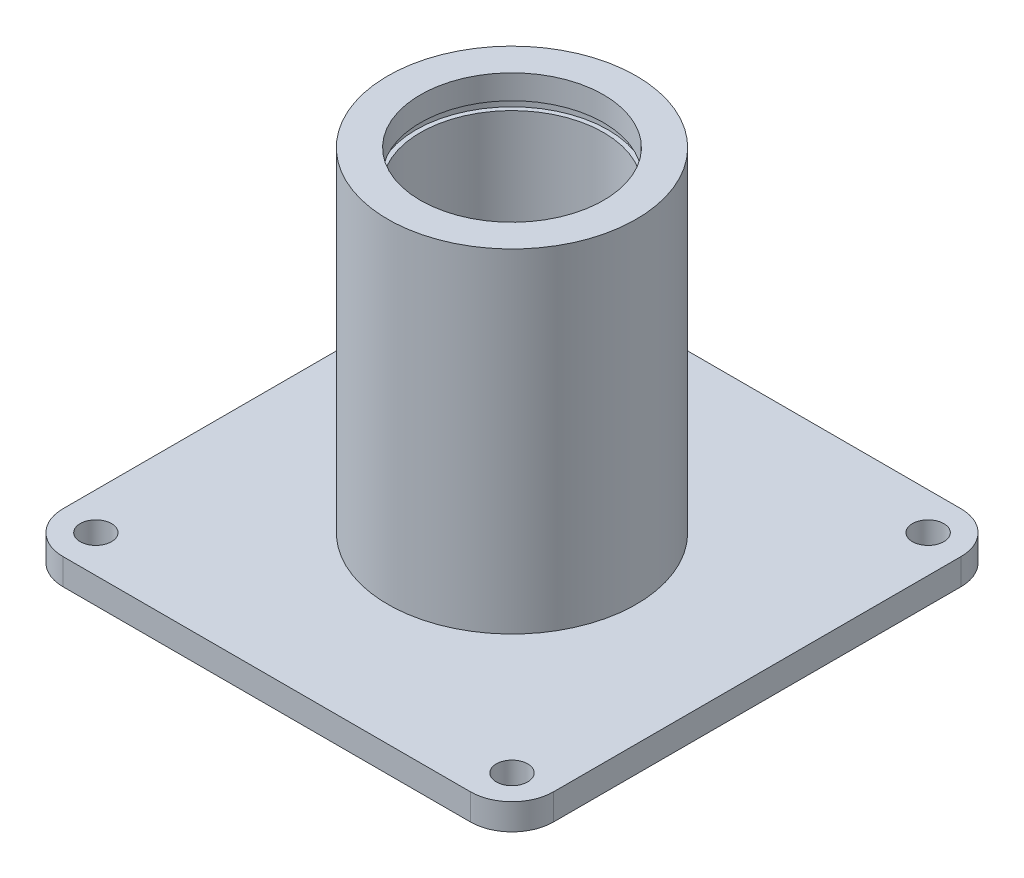
SolidWorks part; units mm, degrees
ref_plane "Front Plane" through (0, 0, 0) normal (0, 0, 1) x (1, 0, 0)
ref_plane "Top Plane" through (0, 0, 0) normal (0, 1, 0) x (1, 0, 0)
ref_plane "Right Plane" through (0, 0, 0) normal (1, 0, 0) x (0, 0, -1)
ref_axis "X" through (88.99, 0, 0) along (-1, 0, 0)
ref_axis "Y" through (0, 55, 0) along (0, -1, 0)
ref_axis "Z" through (0, 0, -88.99) along (0, 0, 1)
sketch "Sketch1" plane through (0, 0, 0) normal (0, 0, 1) x (1, 0, 0)
  line L0 (0, 0) -> (0, 52.8087) construction
  line L1 (-12, 0) -> (-29, 0)
  line L2 (-29, 0) -> (-29, 4)
  line L3 (-29, 4) -> (-19, 4)
  line L4 (-19, 4) -> (-19, 55)
  line L5 (-19, 55) -> (-14, 55)
  line L6 (-14, 55) -> (-14, 51.3)
  line L7 (-14, 30) -> (-12, 30)
  line L8 (-12, 30) -> (-12, 0)
  line L10 (-14, 51.3) -> (-14.7, 51.3)
  line L12 (-14, 50) -> (-14.7, 50)
  line L13 (-14.7, 51.3) -> (-14.7, 50)
  line L14 (-14, 50) -> (-14, 30)
  dimension "D1" = 28
  dimension "D2" = 30
  dimension "D3" = 24
  dimension "D4" = 38
  dimension "D5" = 10
  dimension "D6" = 4
  dimension "D7" = 1.3
  dimension "D8" = 29.4
  dimension "D9" = 55
  dimension "D10" = 20
revolve "Revolve1" add sketch "Sketch1" angle 360 about L0
sketch "Sketch2" plane through (0, 4, 0) normal (0, 1, 0) x (1, 0, 0)
  line L1 (37.5, -37.5) -> (-37.5, -37.5)
  line L2 (37.5, -37.5) -> (37.5, 37.5)
  line L3 (37.5, 37.5) -> (-37.5, 37.5)
  line L4 (-37.5, -37.5) -> (-37.5, 37.5)
  line L5 (37.5, -37.5) -> (-37.5, 37.5) construction
  line L6 (37.5, 37.5) -> (-37.5, -37.5) construction
  circle A0 centre (0, 0) radius 21
  point P0 (0, 0)
  dimension "D1" = 75
extrude "Boss-Extrude1" add sketch "Sketch2" against normal up to surface (4 mm away) up to face at (0, 0, -12)
hole_wizard "M4 Clearance Hole1" positions "Sketch3" profile "Sketch4" hole size "M4" standard "DIN" end condition up to next
sketch "Sketch3" plane through (0, 0, 0) normal (0, -1, 0) x (-1, 0, 0)
  line L2 (31.8198, -31.8198) -> (-31.8198, -31.8198)
  line L3 (31.8198, -31.8198) -> (31.8198, 31.8198)
  line L4 (31.8198, 31.8198) -> (-31.8198, 31.8198)
  line L5 (-31.8198, -31.8198) -> (-31.8198, 31.8198)
  line L6 (31.8198, -31.8198) -> (-31.8198, 31.8198) construction
  line L7 (31.8198, 31.8198) -> (-31.8198, -31.8198) construction
  point P16 (0, 0)
  point P61 (-31.8198, 31.8198)
  point P64 (31.8198, 31.8198)
  point P67 (31.8198, -31.8198)
  point P70 (-31.8198, -31.8198)
  dimension "D1" = 90
sketch "Sketch4" plane through (0, 0, 0) normal (1, 0, 0) x (0, 0, -1)
  line L0 (0, 0) -> (0, 55)
  line L1 (0, 55) -> (2.4, 55)
  line L2 (2.4, 55) -> (2.4, 0)
  line L5 (2.4, 0) -> (0, 0)
  line L11 (0, -6.35) -> (0, 107.95) construction
  dimension "Thru Hole Dia." = 4.8
  dimension "Thru Hole Depth" = 55
fillet "Fillet1" radius 6.35 4 edges at (37.5, 2, 37.5) (-37.5, 2, 37.5) (37.5, 2, -37.5) (-37.5, 2, -37.5)
